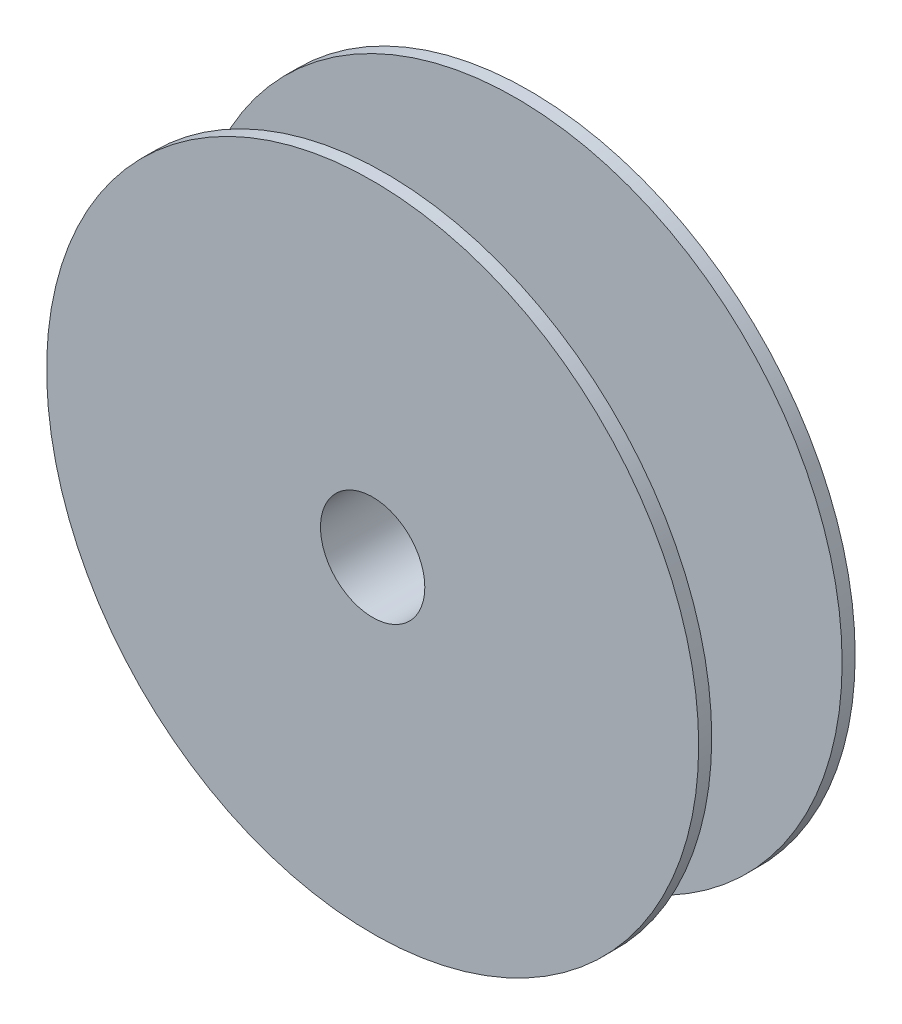
SolidWorks part; units mm, degrees
ref_plane "Front Plane" through (0, 0, 0) normal (0, 0, 1) x (1, 0, 0)
ref_plane "Top Plane" through (0, 0, 0) normal (0, 1, 0) x (1, 0, 0)
ref_plane "Right Plane" through (0, 0, 0) normal (1, 0, 0) x (0, 0, -1)
sketch "Sketch1" plane through (0, 0, 0) normal (0, 0, 1) x (1, 0, 0)
  circle A0 centre (0, 0) radius 125
  circle A1 centre (0, 0) radius 20
  dimension "D1" = 40
  dimension "D2" = 250
extrude "Boss-Extrude1" add sketch "Sketch1" along normal blind 60
shell "Shell1" thickness 5 removed face at (125, 0, 60)
